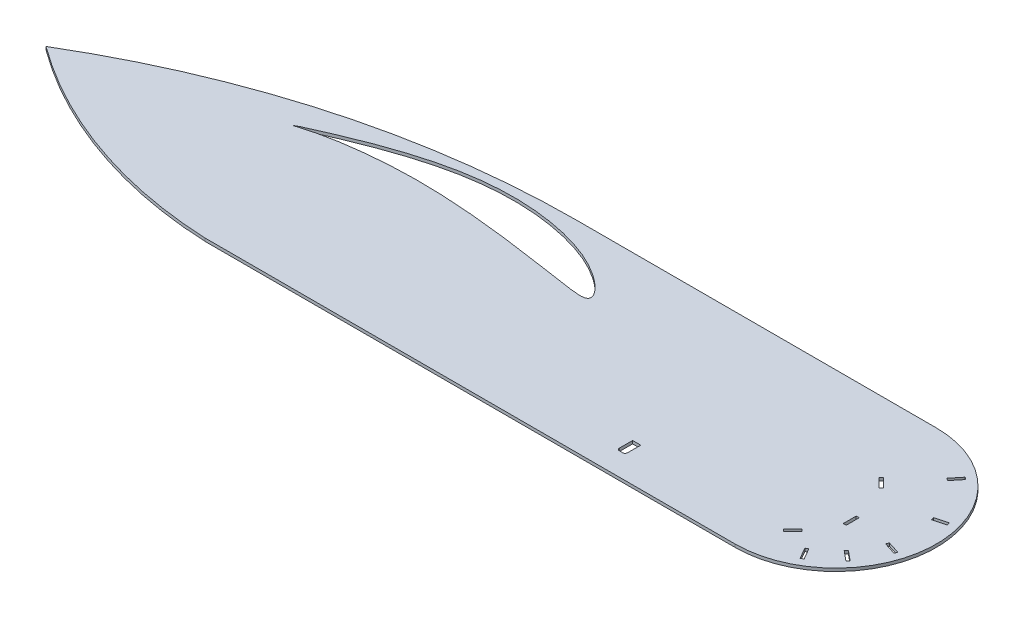
SolidWorks part; units mm, degrees
ref_plane "Front Plane" through (0, 0, 0) normal (0, 0, 1) x (1, 0, 0)
ref_plane "Top Plane" through (0, 0, 0) normal (0, 1, 0) x (1, 0, 0)
ref_plane "Right Plane" through (0, 0, 0) normal (1, 0, 0) x (0, 0, -1)
sketch "Sketch1" plane through (0, 0, 0) normal (0, 1, 0) x (1, 0, 0)
  line L0 (800, 101.2493) -> (0, 101.2493) construction
  line L1 (266.4083, 0) -> (800, 0)
  line L2 (0, 0) -> (0, 202.4986) construction
  line L3 (438.3192, 202.4986) -> (800, 202.4986)
  arc A0 (800, 202.4986) -> (800, 0) centre (800, 101.2493) cw
  arc A2 (266.4083, 0) -> (19.4291, 86.8932) centre (286.1808, 450.645) cw
  arc A4 (19.4291, 86.8932) -> (438.3192, 202.4986) centre (438.3192, -614.2173) cw
  point P1 (382.1275, 200.4327)
  point P7 (0, 0)
  point P8 (800, 210.2521)
  point P12 (438.3192, 202.4986)
  dimension "D1" = 800
extrude "Boss-Extrude1" add sketch "Sketch1" along normal blind 3
sketch "Sketch2" plane through (0, 0, 0) normal (0, -1, 0) x (1, 0, 0)
  line L4 (823.6893, -121.2328) -> (814.4969, -130.4252)
  line L5 (814.4969, -130.4252) -> (816.6182, -132.5465)
  line L6 (816.6182, -132.5465) -> (825.8106, -123.3541)
  line L7 (825.8106, -123.3541) -> (823.6893, -121.2328)
  line L8 (823.6893, -121.2328) -> (814.4969, -130.4252)
  line L9 (814.4969, -130.4252) -> (816.6182, -132.5465)
  line L10 (816.6182, -132.5465) -> (825.8106, -123.3541)
  line L11 (825.8106, -123.3541) -> (823.6893, -121.2328)
  line L20 (841.1972, -32.9616) -> (847.702, -21.706)
  line L21 (847.702, -21.706) -> (845.1046, -20.2049)
  line L22 (845.1046, -20.2049) -> (838.5998, -31.4605)
  line L23 (838.5998, -31.4605) -> (841.1972, -32.9616)
  line L24 (841.1972, -32.9616) -> (847.702, -21.706)
  line L25 (847.702, -21.706) -> (845.1046, -20.2049)
  line L26 (845.1046, -20.2049) -> (838.5998, -31.4605)
  line L27 (838.5998, -31.4605) -> (841.1972, -32.9616)
  line L28 (839.4566, -85.3169) -> (839.4566, -72.3169)
  line L29 (839.4566, -72.3169) -> (836.4566, -72.3169)
  line L30 (836.4566, -72.3169) -> (836.4566, -85.3169)
  line L31 (836.4566, -85.3169) -> (839.4566, -85.3169)
  line L32 (839.4566, -85.3169) -> (839.4566, -72.3169)
  line L33 (839.4566, -72.3169) -> (836.4566, -72.3169)
  line L34 (836.4566, -72.3169) -> (836.4566, -85.3169)
  line L35 (836.4566, -85.3169) -> (839.4566, -85.3169)
  line L37 (212.57, -142.2618) -> (212.57, -142.2948)
  line L38 (212.57, -142.2618) -> (212.57, -142.2948)
  line L40 (658.07, -25.4734) -> (658.07, -38.6734)
  line L41 (663.77, -22.9734) -> (660.57, -22.9734)
  line L42 (666.27, -38.6734) -> (666.27, -25.4734)
  line L43 (658.07, -38.6734) -> (666.27, -38.6734)
  line L44 (658.07, -25.4734) -> (658.07, -38.6734)
  line L45 (663.77, -22.9734) -> (660.57, -22.9734)
  line L46 (666.27, -38.6734) -> (666.27, -25.4734)
  line L47 (658.07, -38.6734) -> (666.27, -38.6734)
  line L188 (849.2146, -164.0056) -> (857.4278, -174.0824) construction
  line L189 (857.4278, -174.0824) -> (859.7532, -172.1871) construction
  line L190 (859.7532, -172.1871) -> (851.54, -162.1102) construction
  line L191 (851.54, -162.1102) -> (849.2146, -164.0056) construction
  line L192 (876.7598, -122.8909) -> (889.3361, -126.1826) construction
  line L193 (889.3361, -126.1826) -> (890.0958, -123.2804) construction
  line L194 (890.0958, -123.2804) -> (877.5194, -119.9887) construction
  line L195 (877.5194, -119.9887) -> (876.7598, -122.8909) construction
  line L196 (876.494, -78.6863) -> (888.8916, -74.7746) construction
  line L197 (888.8916, -74.7746) -> (887.9888, -71.9136) construction
  line L198 (887.9888, -71.9136) -> (875.5913, -75.8253) construction
  line L199 (875.5913, -75.8253) -> (876.494, -78.6863) construction
  line L200 (862.3792, -51.5576) -> (872.3932, -43.2678) construction
  line L201 (872.3932, -43.2678) -> (870.4801, -40.9569) construction
  line L202 (870.4801, -40.9569) -> (860.4662, -49.2467) construction
  line L203 (860.4662, -49.2467) -> (862.3792, -51.5576) construction
  line L204 (822.4089, -44.7346) -> (813.2165, -35.5422) construction
  line L205 (813.2165, -35.5422) -> (811.0952, -37.6635) construction
  line L206 (811.0952, -37.6635) -> (820.2876, -46.8559) construction
  line L207 (820.2876, -46.8559) -> (822.4089, -44.7346) construction
  line L208 (849.2146, -164.0056) -> (857.4278, -174.0824)
  line L209 (857.4278, -174.0824) -> (859.7532, -172.1871)
  line L210 (859.7532, -172.1871) -> (851.54, -162.1102)
  line L211 (851.54, -162.1102) -> (849.2146, -164.0056)
  line L212 (876.7598, -122.8909) -> (889.3361, -126.1826)
  line L213 (889.3361, -126.1826) -> (890.0958, -123.2804)
  line L214 (890.0958, -123.2804) -> (877.5194, -119.9887)
  line L215 (877.5194, -119.9887) -> (876.7598, -122.8909)
  line L216 (876.494, -78.6863) -> (888.8916, -74.7746)
  line L217 (888.8916, -74.7746) -> (887.9888, -71.9136)
  line L218 (887.9888, -71.9136) -> (875.5913, -75.8253)
  line L219 (875.5913, -75.8253) -> (876.494, -78.6863)
  line L220 (862.3792, -51.5576) -> (872.3932, -43.2678)
  line L221 (872.3932, -43.2678) -> (870.4801, -40.9569)
  line L222 (870.4801, -40.9569) -> (860.4662, -49.2467)
  line L223 (860.4662, -49.2467) -> (862.3792, -51.5576)
  line L224 (822.4089, -44.7346) -> (813.2165, -35.5422)
  line L225 (813.2165, -35.5422) -> (811.0952, -37.6635)
  line L226 (811.0952, -37.6635) -> (820.2876, -46.8559)
  line L227 (820.2876, -46.8559) -> (822.4089, -44.7346)
  arc A2 (660.57, -22.9734) -> (658.07, -25.4734) centre (660.57, -25.4734) ccw
  arc A3 (666.27, -25.4734) -> (663.77, -22.9734) centre (663.77, -25.4734) ccw
  arc A4 (660.57, -22.9734) -> (658.07, -25.4734) centre (660.57, -25.4734) ccw
  arc A5 (666.27, -25.4734) -> (663.77, -22.9734) centre (663.77, -25.4734) ccw
  spline S1 degree 3 poles (-935.9633, -1778.8288) (190.5889, -95.3438) (194.6064, -131.763) (215.6642, -144.2206) (218.7234, -145.7779) (222.7838, -147.5804) (227.7591, -149.7808) (233.6732, -152.3729) (243.3346, -156.474) (254.0716, -160.9286) (265.8113, -165.5514) (275.5598, -169.1926) (285.8203, -172.7897) (300.2132, -177.4429) (315.0475, -181.6144) (330.2168, -185.0782) (341.7168, -187.2628) (353.2384, -188.9705) (364.7498, -190.1898) (376.2222, -190.8893) (387.6115, -191.0869) (398.8538, -190.7647) (413.4214, -189.6963) (427.5808, -187.7) (441.1954, -184.8275) (450.8219, -182.3197) (459.9489, -179.4697) (468.5117, -176.2876) (476.4536, -172.8247) (483.7151, -169.1289) (490.2481, -165.2848) (496.0197, -161.4069) (500.998, -157.5857) (505.1476, -153.8841) (508.4473, -150.3827) (510.8522, -147.1808) (512.2305, -144.519) (512.6724, -142.438) (512.366, -140.694) (510.8363, -139.2679) (508.3008, -138.6046) (504.9907, -138.3969) (500.8451, -138.6329) (495.8864, -139.207) (490.1274, -140.0338) (483.6007, -141.0142) (476.346, -142.082) (468.4189, -143.2709) (459.8696, -144.553) (447.4042, -146.414) (434.3028, -148.292) (413.2306, -151.0803) (394.9165, -153.1705) (372.4131, -155.1852) (353.2786, -156.4974) (334.1039, -157.1205) (318.8375, -157.1193) (307.5693, -156.8631) (296.5448, -156.3424) (285.8536, -155.5986) (275.5863, -154.6546) (265.8296, -153.5569) (256.6735, -152.3128) (248.205, -150.9585) (240.5101, -149.5233) (233.6661, -148.0641) (227.7356, -146.6296) (222.7715, -145.2056) (218.7746, -143.9126) (215.7248, -142.9952) (193.3721, -137.343) (166.6151, -157.487) (567.9657, 1824.9991) knots -0.10608 -0.10608 -0.10608 -0.10608 0.001413 0.005226 0.010781 0.017816 0.026461 0.036791 0.048686 0.076639 0.092363 0.109003 0.126387 0.144339 0.181313 0.200023 0.218713 0.237261 0.255692 0.274037 0.292193 0.310133 0.327788 0.362002 0.378421 0.394287 0.409543 0.424114 0.437938 0.450942 0.463044 0.474154 0.484165 0.493024 0.500713 0.507126 0.51213 0.514904 0.517171 0.520262 0.524245 0.529498 0.536092 0.544061 0.553363 0.563905 0.575615 0.58842 0.602227 0.616944 0.648676 0.665501 0.718564 0.736789 0.773513 0.810245 0.828489 0.846493 0.864125 0.881249 0.897725 0.913415 0.928184 0.941897 0.954411 0.965603 0.97535 0.983576 0.990285 0.995433 0.9988 1.100441 1.100441 1.100441 1.100441 only from (212.57, -142.2948) to (212.57, -142.2618)
  spline S2 degree 3 poles (212.57, -142.2948) (212.8151, -142.4601) (213.7215, -143.0713) (215.6642, -144.2206) (218.7234, -145.7779) (222.7838, -147.5804) (227.7591, -149.7808) (233.6732, -152.3729) (243.3346, -156.474) (254.0716, -160.9286) (265.8113, -165.5514) (275.5598, -169.1926) (285.8203, -172.7897) (300.2132, -177.4429) (315.0475, -181.6144) (330.2168, -185.0782) (341.7168, -187.2628) (353.2384, -188.9705) (364.7498, -190.1898) (376.2222, -190.8893) (387.6115, -191.0869) (398.8538, -190.7647) (413.4214, -189.6963) (427.5808, -187.7) (441.1954, -184.8275) (450.8219, -182.3197) (459.9489, -179.4697) (468.5117, -176.2876) (476.4536, -172.8247) (483.7151, -169.1289) (490.2481, -165.2848) (496.0197, -161.4069) (500.998, -157.5857) (505.1476, -153.8841) (508.4473, -150.3827) (510.8522, -147.1808) (512.2305, -144.519) (512.6724, -142.438) (512.366, -140.694) (510.8363, -139.2679) (508.3008, -138.6046) (504.9907, -138.3969) (500.8451, -138.6329) (495.8864, -139.207) (490.1274, -140.0338) (483.6007, -141.0142) (476.346, -142.082) (468.4189, -143.2709) (459.8696, -144.553) (447.4042, -146.414) (434.3028, -148.292) (413.2306, -151.0803) (394.9165, -153.1705) (372.4131, -155.1852) (353.2786, -156.4974) (334.1039, -157.1205) (318.8375, -157.1193) (307.5693, -156.8631) (296.5448, -156.3424) (285.8536, -155.5986) (275.5863, -154.6546) (265.8296, -153.5569) (256.6735, -152.3128) (248.205, -150.9585) (240.5101, -149.5233) (233.6661, -148.0641) (227.7356, -146.6296) (222.7715, -145.2056) (218.7746, -143.9126) (215.7248, -142.9952) (213.7534, -142.4967) (212.8162, -142.3107) (212.57, -142.2618) knots 0 0 0 0 0.001413 0.005226 0.010781 0.017816 0.026461 0.036791 0.048686 0.076639 0.092363 0.109003 0.126387 0.144339 0.181313 0.200023 0.218713 0.237261 0.255692 0.274037 0.292193 0.310133 0.327788 0.362002 0.378421 0.394287 0.409543 0.424114 0.437938 0.450942 0.463044 0.474154 0.484165 0.493024 0.500713 0.507126 0.51213 0.514904 0.517171 0.520262 0.524245 0.529498 0.536092 0.544061 0.553363 0.563905 0.575615 0.58842 0.602227 0.616944 0.648676 0.665501 0.718564 0.736789 0.773513 0.810245 0.828489 0.846493 0.864125 0.881249 0.897725 0.913415 0.928184 0.941897 0.954411 0.965603 0.97535 0.983576 0.990285 0.995433 0.9988 1 1 1 1
  dimension "D1" = 0
  dimension "D2" = 0
  dimension "D3" = 0
  dimension "D4" = 0
  dimension "D5" = 0
extrude "Cut-Extrude1" cut sketch "Sketch2" against normal through all
